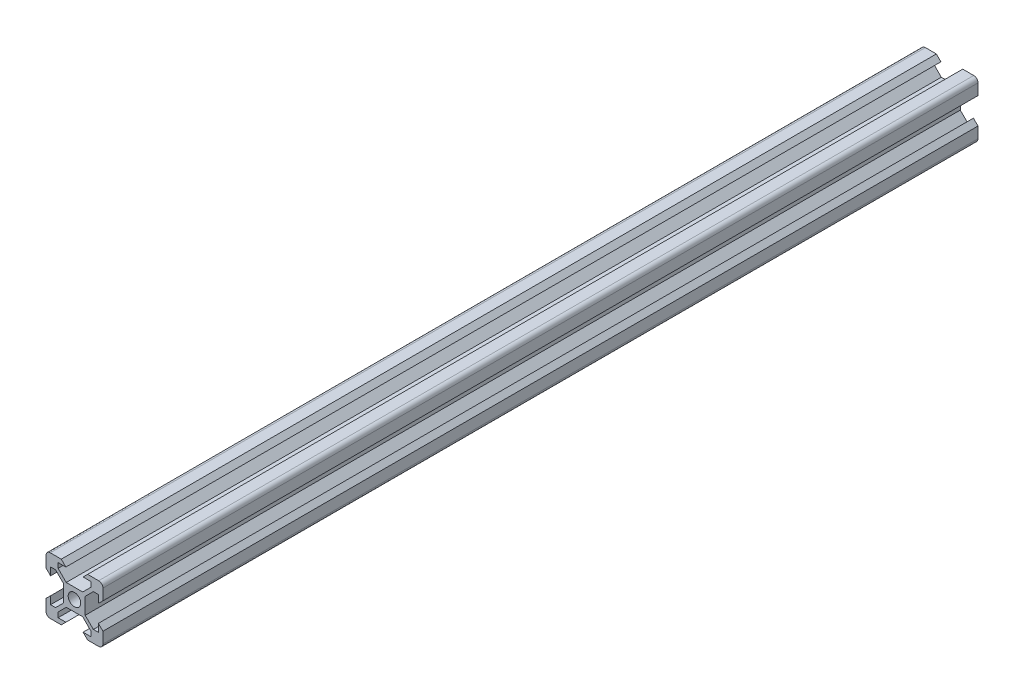
SolidWorks part; units mm, degrees
ref_plane "Front Plane" through (0, 0, 0) normal (0, 0, 1) x (1, 0, 0)
ref_plane "Top Plane" through (0, 0, 0) normal (0, 1, 0) x (1, 0, 0)
ref_plane "Right Plane" through (0, 0, 0) normal (1, 0, 0) x (0, 0, -1)
sketch "Sketch1" plane through (0, 0, 0) normal (0, 0, 1) x (1, 0, 0)
  line L0 (-5.7847, 7.544) -> (-11.512, 13.2713)
  line L1 (-7.544, 7.544) -> (7.544, 7.544)
  line L2 (-7.544, 7.544) -> (-7.544, -7.544)
  line L3 (-7.544, -7.544) -> (7.544, -7.544)
  line L4 (7.544, 7.544) -> (7.544, -7.544)
  line L5 (-7.544, 7.544) -> (7.544, -7.544) construction
  line L6 (-7.544, -7.544) -> (7.544, 7.544) construction
  line L7 (-11.512, 13.2713) -> (-11.512, 16.8)
  line L8 (-11.512, 16.8) -> (-6.052, 16.8)
  line L9 (-6.052, 16.8) -> (-9.252, 20)
  line L10 (-9.252, 20) -> (-17, 20)
  line L11 (-20, 17) -> (-20, 9.252)
  line L12 (-20, 9.252) -> (-16.8, 6.052)
  line L13 (-16.8, 6.052) -> (-16.8, 11.512)
  line L14 (-16.8, 11.512) -> (-13.2713, 11.512)
  line L15 (-13.2713, 11.512) -> (-7.544, 5.7847)
  line L16 (-19.1213, 19.1213) -> (0, 0) construction
  line L17 (13.2713, 11.512) -> (16.8, 11.512)
  line L18 (20, 9.252) -> (20, 17)
  line L19 (17, 20) -> (9.252, 20)
  line L20 (9.252, 20) -> (6.052, 16.8)
  line L21 (6.052, 16.8) -> (11.512, 16.8)
  line L22 (11.512, 16.8) -> (11.512, 13.2713)
  line L23 (11.512, 13.2713) -> (5.7847, 7.544)
  line L24 (7.544, 5.7847) -> (13.2713, 11.512)
  line L25 (16.8, 11.512) -> (16.8, 6.052)
  line L26 (16.8, 6.052) -> (20, 9.252)
  line L27 (19.1213, 19.1213) -> (0, 0) construction
  line L28 (11.512, -13.2713) -> (11.512, -16.8)
  line L29 (9.252, -20) -> (17, -20)
  line L30 (20, -17) -> (20, -9.252)
  line L31 (20, -9.252) -> (16.8, -6.052)
  line L32 (16.8, -6.052) -> (16.8, -11.512)
  line L33 (16.8, -11.512) -> (13.2713, -11.512)
  line L34 (13.2713, -11.512) -> (7.544, -5.7847)
  line L35 (5.7847, -7.544) -> (11.512, -13.2713)
  line L36 (11.512, -16.8) -> (6.052, -16.8)
  line L37 (6.052, -16.8) -> (9.252, -20)
  line L38 (19.1213, -19.1213) -> (0, 0) construction
  line L39 (-13.2713, -11.512) -> (-16.8, -11.512)
  line L40 (-20, -9.252) -> (-20, -17)
  line L41 (-17, -20) -> (-9.252, -20)
  line L42 (-9.252, -20) -> (-6.052, -16.8)
  line L43 (-6.052, -16.8) -> (-11.512, -16.8)
  line L44 (-11.512, -16.8) -> (-11.512, -13.2713)
  line L45 (-11.512, -13.2713) -> (-5.7847, -7.544)
  line L46 (-7.544, -5.7847) -> (-13.2713, -11.512)
  line L47 (-16.8, -11.512) -> (-16.8, -6.052)
  line L48 (-16.8, -6.052) -> (-20, -9.252)
  line L49 (-19.1213, -19.1213) -> (0, 0) construction
  circle A0 centre (0, 0) radius 4.4
  arc A1 (-17, 20) -> (-20, 17) centre (-17, 17) ccw
  arc A2 (20, 17) -> (17, 20) centre (17, 17) ccw
  arc A3 (17, -20) -> (20, -17) centre (17, -17) ccw
  arc A4 (-20, -17) -> (-17, -20) centre (-17, -17) ccw
  point P66 (0, 0)
  dimension "D1" = 8.8
  dimension "D8" = 3
  dimension "D2" = 15.088
  dimension "D3" = 2.488
  dimension "D4" = 8.488
  dimension "D5" = 3.2
  dimension "D6" = 20
  dimension "D7" = 15.2
  dimension "D9" = 4
extrude "Boss-Extrude1" add sketch "Sketch1" along normal mid plane 615 contours L10 A1 L11 L12 L13 L14 L15 L2 L1 L0 L7 L8 L9 | L18 A2 L19 L20 L21 L22 L23 L1 L4 L24 L17 L25 L26 | L40 A4 L41 L42 L43 L44 L45 L3 L2 L46 L39 L47 L48 | L29 A3 L30 L31 L32 L33 L34 L4 L3 L35 L28 L36 L37 | L4 L1 L2 L3 A0 region at (-14.3184, 14.3184, 0) region at (0, 7.3306, 0) region at (14.3184, 14.3184, 0) region at (-14.3184, -14.3184, 0) region at (14.3184, -14.3184, 0)
equation "\"longitud\"= 600mm"
